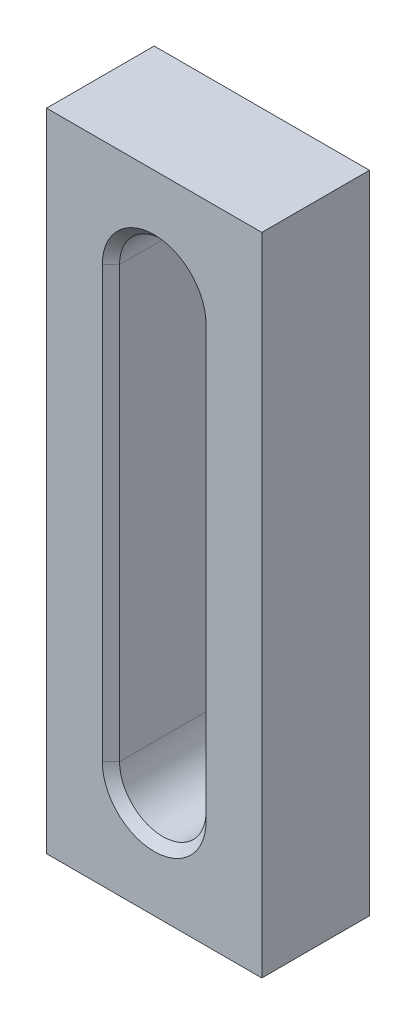
SolidWorks part; units mm, degrees
ref_plane "Спереди" through (0, 0, 0) normal (0, 0, 1) x (1, 0, 0)
ref_plane "Сверху" through (0, 0, 0) normal (0, 1, 0) x (1, 0, 0)
ref_plane "Справа" through (0, 0, 0) normal (1, 0, 0) x (0, 0, -1)
sketch "Эскиз1" plane through (0, 0, 0) normal (0, 0, 1) x (1, 0, 0)
  line L1 (0, 0) -> (50, 0)
  line L2 (0, 0) -> (0, 150)
  line L3 (0, 150) -> (50, 150)
  line L4 (50, 0) -> (50, 150)
  dimension "D1" = 50
  dimension "D2" = 150
extrude "Бобышка-Вытянуть1" add sketch "Эскиз1" along normal blind 25
sketch "Эскиз2" plane through (0, 0, 25) normal (0, 0, 1) x (1, 0, 0)
  line L1 (14.95, 25) -> (14.95, 125)
  line L2 (35.05, 25) -> (35.05, 125)
  line L3 (0, 150) -> (0, 0) construction
  line L4 (0, 0) -> (50, 0) construction
  arc A0 (14.95, 25) -> (35.05, 25) centre (25, 25) ccw
  arc A1 (14.95, 125) -> (35.05, 125) centre (25, 125) cw
  point P7 (14.95, 75)
  point P10 (35.05, 75)
  dimension "D1" = 25
  dimension "D2" = 25
extrude "Вырез-Вытянуть1" cut sketch "Эскиз2" against normal through all
chamfer "Фаска1" distance 2 angle 45 8 edges at (14.95, 75, 0) (25, 14.95, 0) (25, 135.05, 0) (35.05, 75, 0) (35.05, 75, 25) (25, 135.05, 25) (25, 14.95, 25) (14.95, 75, 25)
